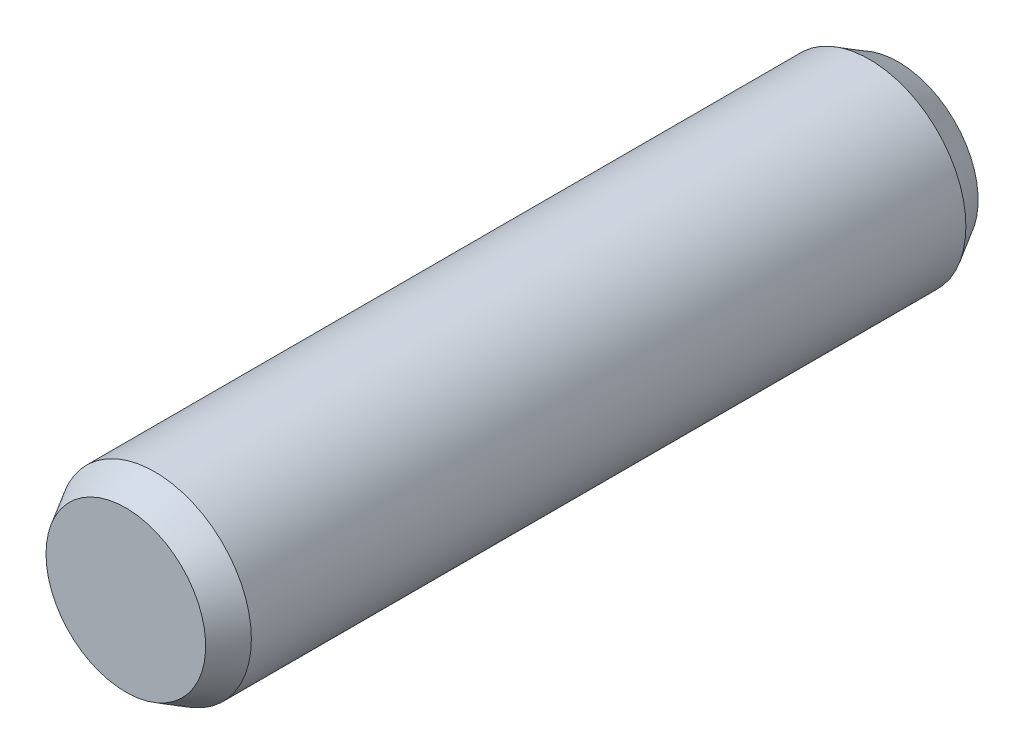
SolidWorks part; units mm, degrees
ref_plane "Ebene vorne" through (0, 0, 0) normal (0, 0, 1) x (1, 0, 0)
ref_plane "Ebene oben" through (0, 0, 0) normal (0, 1, 0) x (1, 0, 0)
ref_plane "Ebene rechts" through (0, 0, 0) normal (1, 0, 0) x (0, 0, -1)
sketch "Skizze1" plane through (0, 0, 0) normal (1, 0, 0) x (0, 0, -1)
  line L0 (-37, 10) -> (37, 10)
  line L1 (37, 10) -> (40, 8.2679)
  line L2 (40, 8.2679) -> (40, 0)
  line L3 (55, 0) -> (-55, 0) construction
  line L4 (40, 0) -> (-40, 0)
  line L5 (-40, 0) -> (-40, 8.2679)
  line L6 (-40, 8.2679) -> (-37, 10)
  line L7 (0, 55) -> (0, -55) construction
  line L8 (0, 50.8437) -> (0, -37.1399) construction
  line L9 (-41.3685, 0) -> (68.2338, 0) construction
  dimension "D1" = 10
  dimension "D2" = 80
  dimension "D5" = 3
  dimension "D3" = 30
revolve "Rotation1" add sketch "Skizze1" angle 360 about L4
sketch "Skizze2" plane through (0, 0, 0) normal (0, 1, 0) x (1, 0, 0)
  line L1 (0, -55) -> (0, 55) construction
  line L2 (-8.2679, -40) -> (8.2679, -40) construction
  line L3 (8.2679, 40) -> (-8.2679, 40) construction
  circle A1 centre (0, -35) radius 1.5
  circle A2 centre (0, 34) radius 1.5
  dimension "D1" = 3
  dimension "D2" = 5
  dimension "D3" = 6
extrude "Schnitt-Linear austragen1" [suppressed] cut sketch "Skizze2" against normal blind 10 and the other way blind 10
equation "\"diameter\"= 20"
equation "\"length\"= 80"
equation "\"chamfer_height_30\"= 3"
equation "\"hole_diameter\"= 3"
equation "\"hole_distance\"= 5"
equation "\"D1@Skizze1\"= \"diameter\" / 2"
equation "\"D2@Skizze1\"= \"length\""
equation "\"D5@Skizze1\"= \"chamfer_height_30\""
equation "\"D1@Skizze2\"= \"hole_diameter\""
equation "\"D2@Skizze2\"= \"hole_distance\""
